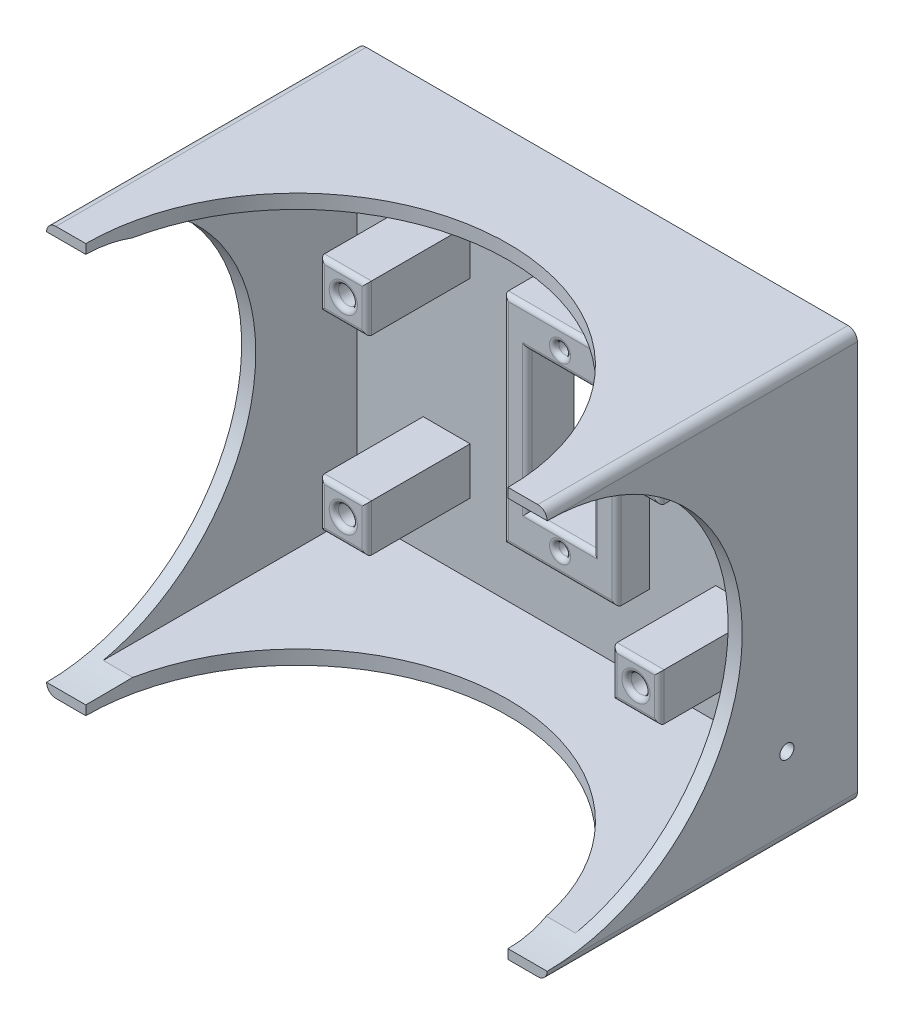
SolidWorks part; units mm, degrees
ref_plane "Plan de face" through (0, 0, 0) normal (0, 0, 1) x (1, 0, 0)
ref_plane "Plan de dessus" through (0, 0, 0) normal (0, 1, 0) x (1, 0, 0)
ref_plane "Plan de droite" through (0, 0, 0) normal (1, 0, 0) x (0, 0, -1)
sketch "Esquisse1" plane through (0, 0, 0) normal (0, 0, 1) x (1, 0, 0)
  line L20 (-105.3394, -69.4039) -> (-4.8344, -69.4039)
  line L21 (-105.3394, -69.4039) -> (-105.3394, 11.5961)
  line L22 (-105.3394, 11.5961) -> (-4.8344, 11.5961)
  line L23 (-4.8344, -69.4039) -> (-4.8344, 11.5961)
  line L32 (-108.3394, -72.4039) -> (-1.8344, -72.4039)
  line L33 (-108.3394, -72.4039) -> (-108.3394, 14.5961)
  line L34 (-108.3394, 14.5961) -> (-1.8344, 14.5961)
  line L35 (-1.8344, -72.4039) -> (-1.8344, 14.5961)
  line L40 (-48.0894, -14.1539) -> (-62.0894, -14.1539)
  line L41 (-48.0894, -14.1539) -> (-48.0894, -44.1539)
  line L42 (-48.0894, -44.1539) -> (-62.0894, -44.1539)
  line L43 (-62.0894, -14.1539) -> (-62.0894, -44.1539)
  line L46 (-91.2144, -3.9039) -> (-81.2144, -3.9039)
  line L47 (-91.2144, -3.9039) -> (-91.2144, -13.9039)
  line L50 (-91.2144, -13.9039) -> (-81.2144, -13.9039)
  line L51 (-81.2144, -3.9039) -> (-81.2144, -13.9039)
  line L54 (-28.9644, -3.9039) -> (-18.9644, -3.9039)
  line L55 (-28.9644, -3.9039) -> (-28.9644, -13.9039)
  line L58 (-28.9644, -13.9039) -> (-18.9644, -13.9039)
  line L59 (-18.9644, -3.9039) -> (-18.9644, -13.9039)
  line L60 (-67.0894, -52.1539) -> (-43.0894, -52.1539)
  line L61 (-67.0894, -52.1539) -> (-67.0894, -6.1539)
  line L62 (-67.0894, -6.1539) -> (-43.0894, -6.1539)
  line L63 (-43.0894, -52.1539) -> (-43.0894, -6.1539)
  line L64 (-28.9644, -44.4039) -> (-18.9644, -44.4039)
  line L65 (-28.9644, -44.4039) -> (-28.9644, -54.4039)
  line L66 (-28.9644, -54.4039) -> (-18.9644, -54.4039)
  line L67 (-18.9644, -44.4039) -> (-18.9644, -54.4039)
  line L68 (-91.2144, -44.4039) -> (-81.2144, -44.4039)
  line L69 (-91.2144, -44.4039) -> (-91.2144, -54.4039)
  line L70 (-91.2144, -54.4039) -> (-81.2144, -54.4039)
  line L71 (-81.2144, -44.4039) -> (-81.2144, -54.4039)
  circle A6 centre (-86.2144, -8.9039) radius 2
  circle A7 centre (-23.9644, -8.9039) radius 2
  circle A8 centre (-86.2144, -49.4039) radius 2
  circle A9 centre (-23.9644, -49.4039) radius 2
  circle A10 centre (-55.0894, -47.6539) radius 1.25
  circle A11 centre (-55.0894, -10.6539) radius 1.25
  point P38 (0, 0)
  point P88 (0, 0)
  dimension "D10" = 19.13
  dimension "D19" = 100.505
  dimension "D60" = 37
  dimension "D7" = 62.25
  dimension "D8" = 20
  dimension "D9" = 20
  dimension "D11" = 81
  dimension "D12" = 19.125
  dimension "D13" = 19.13
  dimension "D14" = 19.125
  dimension "D15" = 3
  dimension "D16" = 3
  dimension "D17" = 3
  dimension "D18" = 81
  dimension "D20" = 31.125
  dimension "D21" = 31.125
  dimension "D22" = 2.25
  dimension "D23" = 2.25
  dimension "D26" = 3
  dimension "D28" = 10
  dimension "D32" = 14
  dimension "D33" = 30
  dimension "D35" = 10
  dimension "D36" = 5
  dimension "D37" = 5
  dimension "D38" = 10
  dimension "D39" = 10
  dimension "D40" = 5
  dimension "D41" = 5
  dimension "D42" = 10
  dimension "D44" = 5
  dimension "D45" = 8
  dimension "D46" = 5
  dimension "D47" = 8
  dimension "D49" = 62.25
  dimension "D50" = 40.5
  dimension "D51" = 40.5
  dimension "D53" = 10
  dimension "D54" = 5
  dimension "D55" = 5
  dimension "D56" = 10
  dimension "D57" = 10
  dimension "D58" = 5
  dimension "D59" = 5
  dimension "D61" = 7
  dimension "D62" = 3.5
  dimension "D63" = 7
extrude "Boss.-Extru.1" add sketch "Esquisse1" along normal blind 66 contours L32 L35 L34 L33 L23 L20 L21 L22 region at (-106.9642, -28.9039, 0)
extrude "Boss.-Extru.2" add sketch "Esquisse1<35>" along normal blind 3 contours L20 L23 L22 L21 region at (-104.0486, -28.9039, 0)
sketch "Esquisse1<35>" plane through (0, 0, 0) normal (0, 0, 1) x (1, 0, 0) same geometry as "Esquisse1"
fillet "Congé1" radius 2 1 edges at (-108.3394, -72.4039, 33)
fillet "Congé2" radius 2 1 edges at (-108.3394, 14.5961, 33)
fillet "Congé4" radius 2 1 edges at (-1.8344, 14.5961, 33)
fillet "Congé5" radius 2 1 edges at (-1.8344, -72.4039, 33)
sketch "Esquisse3" plane through (0, -72.4039, 0) normal (0, -1, 0) x (1, 0, 0)
  line L0 (-106.3394, 66) -> (-3.8344, 66) construction
  circle A0 centre (-55.0869, 66) radius 44.9177
extrude "Enlèv. mat.-Extru.2" cut sketch "Esquisse3" against normal blind 111 contours A0
sketch "Esquisse4" plane through (-1.8344, 0, 0) normal (1, 0, 0) x (0, 0, -1)
  line L0 (-66, -70.4039) -> (-66, 12.5961) construction
  circle A0 centre (-66, -28.9039) radius 41.5
extrude "Enlèv. mat.-Extru.3" cut sketch "Esquisse4" against normal blind 111 contours A0
sketch "Esquisse5" plane through (-108.3394, 0, 0) normal (-1, 0, 0) x (0, 0, 1)
  line L0 (66, 12.5961) -> (0, 12.5961) construction
  line L1 (0, -70.4039) -> (0, 12.5961) construction
  circle A0 centre (15, -2.4039) radius 1.5
  dimension "D1" = 15
  dimension "D2" = 15
extrude "Enlèv. mat.-Extru.6" cut sketch "Esquisse5" against normal blind 5
sketch "Esquisse8" plane through (-1.8344, 0, 0) normal (1, 0, 0) x (0, 0, -1)
  line L0 (-66, -70.4039) -> (0, -70.4039) construction
  line L1 (0, -70.4039) -> (0, 12.5961) construction
  circle A0 centre (-15, -55.4039) radius 1.5
  dimension "D1" = 15
  dimension "D2" = 15
extrude "Enlèv. mat.-Extru.7" cut sketch "Esquisse8" against normal blind 15 contours A0
extrude "Boss.-Extru.9" add sketch "Esquisse1<44>" along normal blind 10 contours L60 L63 L62 L61 L43 L40 L41 L42 region at (-66.5706, -29.1539, 0)
sketch "Esquisse1<44>" plane through (0, 0, 0) normal (0, 0, 1) x (1, 0, 0) same geometry as "Esquisse1"
extrude "Boss.-Extru.10" add sketch "Esquisse1<45>" along normal blind 25 contours L51 L46 L47 L50 A6 | L71 L68 L69 L70 A8 | L59 L54 L55 L58 A7 | L67 L64 L65 L66 A9 region at (-86.2144, -4.0453, 0) region at (-23.9644, -4.0453, 0) region at (-23.9644, -44.5453, 0) region at (-86.2144, -44.5453, 0)
sketch "Esquisse1<45>" plane through (0, 0, 0) normal (0, 0, 1) x (1, 0, 0) same geometry as "Esquisse1"
extrude "Boss.-Extru.11" add sketch "Esquisse1<46>" along normal blind 10 contours A8 | A6 | A7 | A9 | A7 region at (-86.2144, -8.9039, 0) region at (-23.9644, -8.9039, 0) region at (-86.2144, -49.4039, 0) region at (-23.9644, -49.4039, 0)
sketch "Esquisse1<46>" plane through (0, 0, 0) normal (0, 0, 1) x (1, 0, 0) same geometry as "Esquisse1"
extrude "Boss.-Extru.12" add sketch "Esquisse1<51>" along normal blind 5 contours A10 | A11 region at (-55.0894, -47.6539, 0)
sketch "Esquisse1<51>" plane through (0, 0, 0) normal (0, 0, 1) x (1, 0, 0) same geometry as "Esquisse1"
fillet "Congé9" radius 1 20 edges at (-86.2144, -54.4039, 25) (-91.2144, -49.4039, 25) (-86.2144, -44.4039, 25) (-81.2144, -49.4039, 25) (-84.2144, -49.4039, 25) (-86.2144, -13.9039, 25) (-91.2144, -8.9039, 25) (-86.2144, -3.9039, 25) (-81.2144, -8.9039, 25) (-84.2144, -8.9039, 25) (-23.9644, -54.4039, 25) (-28.9644, -49.4039, 25) (-23.9644, -44.4039, 25) (-18.9644, -49.4039, 25) (-21.9644, -49.4039, 25) (-23.9644, -13.9039, 25) (-28.9644, -8.9039, 25) (-23.9644, -3.9039, 25) (-18.9644, -8.9039, 25) (-21.9644, -8.9039, 25)
fillet "Congé10" radius 1 10 edges at (-67.0894, -29.1539, 10) (-55.0894, -6.1539, 10) (-43.0894, -29.1539, 10) (-55.0894, -52.1539, 10) (-55.0894, -44.1539, 10) (-48.0894, -29.1539, 10) (-55.0894, -14.1539, 10) (-62.0894, -29.1539, 10) (-53.8394, -47.6539, 10) (-53.8394, -10.6539, 10)
